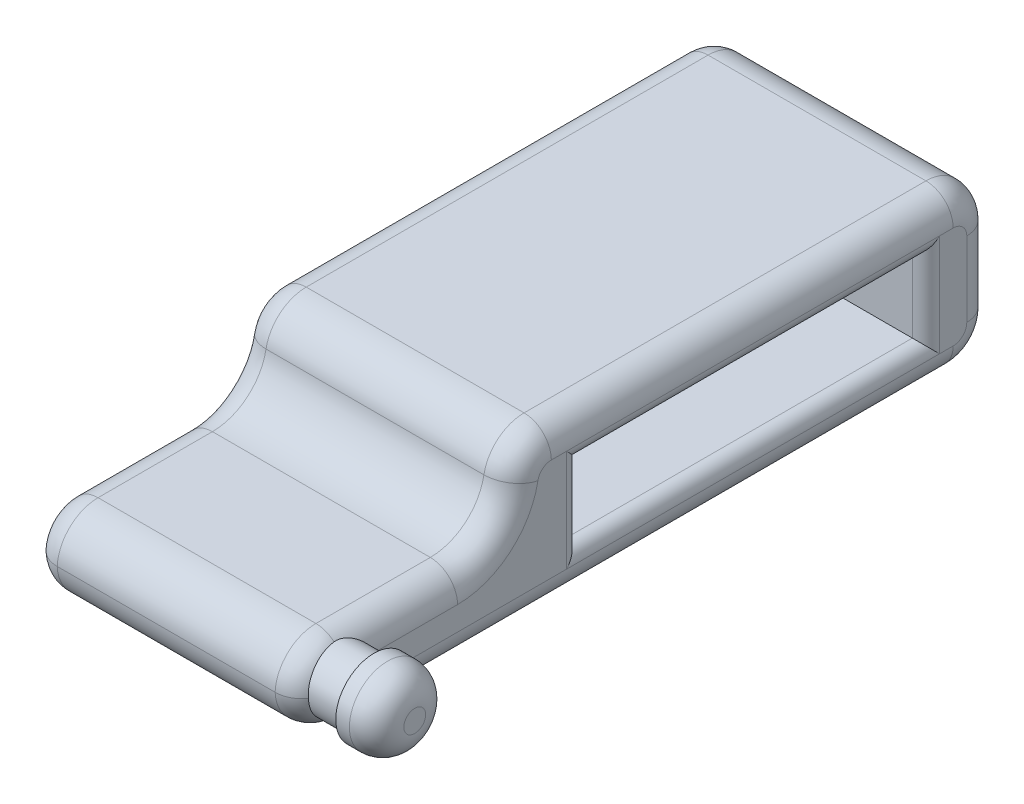
SolidWorks part; units mm, degrees
ref_plane "Front Plane" through (0, 0, 0) normal (0, 0, 1) x (1, 0, 0)
ref_plane "Top Plane" through (0, 0, 0) normal (0, 1, 0) x (1, 0, 0)
ref_plane "Right Plane" through (0, 0, 0) normal (1, 0, 0) x (0, 0, -1)
sketch "Sketch1" plane through (0, 0, 0) normal (0, 1, 0) x (1, 0, 0)
  line L0 (20.6264, -9.9753) -> (0.6264, -9.9753)
  line L1 (0.6264, 15.4247) -> (20.6264, 15.4247)
  line L2 (0.6264, 15.4247) -> (0.6264, -35.3753)
  line L3 (0.6264, -35.3753) -> (20.6264, -35.3753)
  line L4 (20.6264, 15.4247) -> (20.6264, -35.3753)
  dimension "D1" = 50.8
  dimension "D2" = 20
extrude "Boss-Extrude1" add sketch "Sketch1" along normal blind 11.5 contours L4 L1 L2 L0 region at (10.6264, 0, -2.7247)
extrude "Boss-Extrude2" add sketch "Sketch1<3>" along normal blind 5.75 contours L4 L0 L2 L3 region at (10.6264, 0, 22.6753)
sketch "Sketch1<3>" plane through (0, 0, 0) normal (0, 1, 0) x (1, 0, 0) same geometry as "Sketch1"
sketch "Sketch3" plane through (0, 0, 9.9753) normal (0, 0, 1) x (1, 0, 0)
  line L1 (20.6264, 5.75) -> (0.6264, 5.75)
  line L2 (20.6264, 5.75) -> (20.6264, 11.5)
  line L3 (20.6264, 11.5) -> (0.6264, 11.5)
  line L4 (0.6264, 5.75) -> (0.6264, 11.5)
extrude "Boss-Extrude3" add sketch "Sketch3" along normal blind 10
sketch "Sketch4" plane through (20.6264, 0, 0) normal (1, 0, 0) x (0, 0, -1)
  line L0 (15.4247, 11.5) -> (15.4247, 0) construction
  line L1 (-14.9753, 8.5) -> (10.4247, 8.5)
  line L2 (-14.9753, 8.5) -> (-14.9753, 3)
  line L3 (-14.9753, 3) -> (10.4247, 3)
  line L4 (10.4247, 8.5) -> (10.4247, 3)
  line L5 (15.4247, 11.5) -> (-19.9753, 11.5) construction
  dimension "D1" = 5.5
  dimension "D2" = 25.4
  dimension "D3" = 5
  dimension "D4" = 3
extrude "Cut-Extrude1" cut sketch "Sketch4" against normal through all
fillet "Fillet1" radius 1 4 edges at (20.6264, 5.75, -10.4247) (20.6264, 8.5, 2.2753) (20.6264, 5.75, 14.9753) (20.6264, 3, 2.2753)
fillet "Fillet2" radius 1 4 edges at (0.6264, 8.5, 2.2753) (0.6264, 5.75, 14.9753) (0.6264, 5.75, -10.4247) (0.6264, 3, 2.2753)
fillet "Fillet3" radius 3 1 edges at (10.6264, 11.5, -15.4247)
fillet "Fillet4" radius 3 1 edges at (10.6264, 0, -15.4247)
fillet "Fillet5" radius 4 1 edges at (10.6264, 5.75, 19.9753)
fillet "Fillet6" radius 3 1 edges at (10.6264, 11.5, 19.9753)
sketch "Sketch6" plane through (20.6264, 0, 0) normal (1, 0, 0) x (0, 0, -1)
  circle A0 centre (-32.2438, 2.9496) radius 2.2991
extrude "Boss-Extrude4" add sketch "Sketch6" along normal blind 2
fillet "Fillet7" radius 3 2 edges at (10.6264, 0, 35.3753) (10.6264, 5.75, 35.3753)
sketch "Sketch8" plane through (22.6264, 0, 0) normal (1, 0, 0) x (0, 0, -1)
  circle A0 centre (-32.1181, 2.9236) radius 2.8
extrude "Boss-Extrude6" add sketch "Sketch8" along normal blind 3
fillet "Fillet9" radius 2 1 edges at (25.6264, 2.9236, 29.3181)
fillet "Fillet10" radius 2 10 edges at (0.6264, 0.8349, 34.452) (0.6264, 0, 9.9753) (0.6264, 0.8787, -14.546) (0.6264, 5.75, -15.4247) (0.6264, 10.6213, -14.546) (0.6264, 4.9151, 34.452) (0.6264, 6.6794, 21.4118) (0.6264, 10.8029, 19.0104) (0.6264, 11.5, 2.3316)
fillet "Fillet11" radius 2 8 edges at (20.6264, 0, 9.9753) (20.6264, 0.8787, -14.546) (20.6264, 5.75, -15.4247) (20.6264, 10.6213, -14.546) (20.6264, 6.6794, 21.4118) (20.6264, 10.8029, 19.0104) (20.6264, 11.5, 2.3316)
